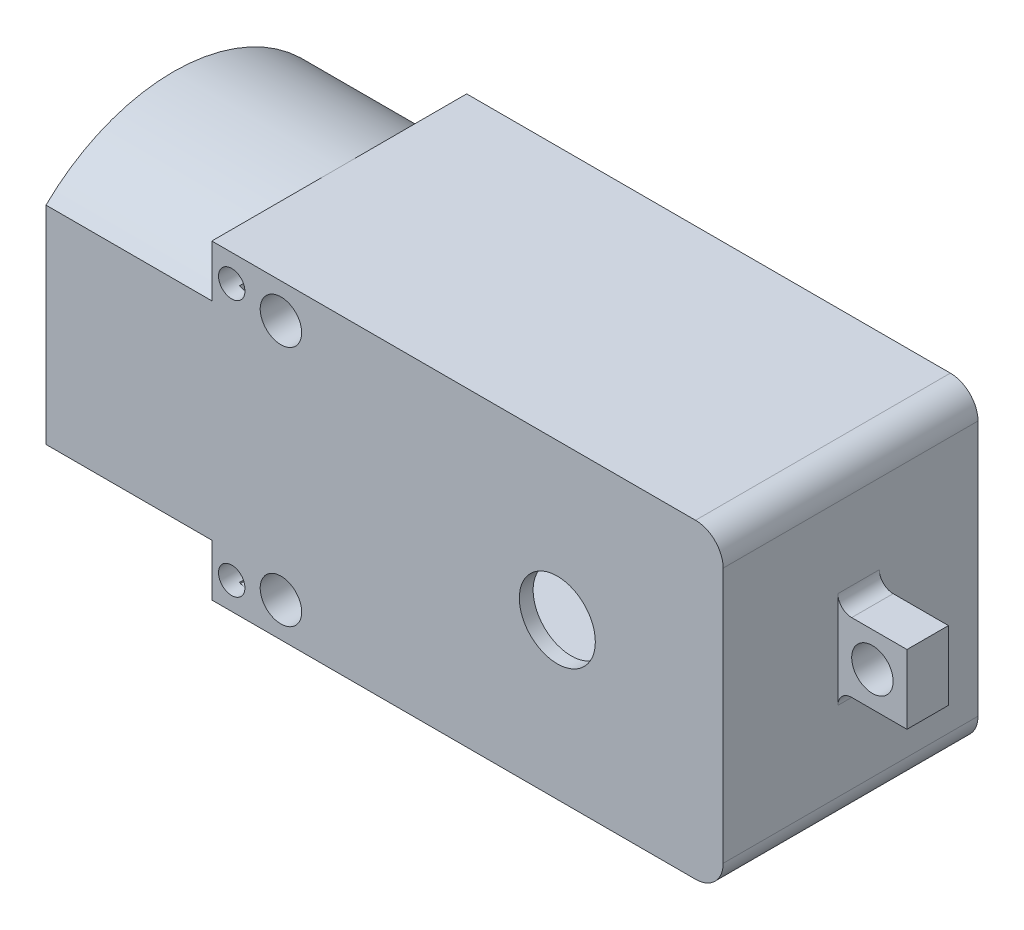
SolidWorks part; units mm, degrees
ref_plane "Front Plane" through (0, 0, 0) normal (0, 0, 1) x (1, 0, 0)
ref_plane "Top Plane" through (0, 0, 0) normal (0, 1, 0) x (1, 0, 0)
ref_plane "Right Plane" through (0, 0, 0) normal (1, 0, 0) x (0, 0, -1)
sketch "Sketch1" plane through (0, 0, 0) normal (0, 0, 1) x (1, 0, 0)
  line L1 (17.5, -11.25) -> (-17.5, -11.25)
  line L2 (19.5, -9.25) -> (19.5, 9.25)
  line L3 (17.5, 11.25) -> (-17.5, 11.25)
  line L4 (-17.5, -11.25) -> (-17.5, 11.25)
  line L5 (0, 11.25) -> (0, -11.25) construction
  line L6 (19.5, 0) -> (-17.5, 0) construction
  arc A0 (17.5, -11.25) -> (19.5, -9.25) centre (17.5, -9.25) ccw
  arc A1 (19.5, 9.25) -> (17.5, 11.25) centre (17.5, 9.25) ccw
  circle A2 centre (-12.5, 8.75) radius 1.5
  circle A3 centre (-12.5, -8.75) radius 1.5
  point P0 (0, 0)
  dimension "D1" = 2
  dimension "D4" = 3
  dimension "D6" = 17.5
  dimension "D2" = 22.5
  dimension "D3" = 37
  dimension "D5" = 5
extrude "Boss-Extrude1" add sketch "Sketch1" along normal mid plane 18.44
ref_plane "Plane1" through (0, 0, -0.58) normal (0, 0, 1) x (1, 0, 0)
sketch "Sketch2" plane through (-17.5, 0, 0) normal (-1, 0, 0) x (0, 0, 1)
  line L0 (9.22, -7.5) -> (9.22, 7.5)
  line L1 (-9.22, 11.25) -> (-9.22, -11.25) construction
  line L2 (9.22, 11.25) -> (9.22, -11.25) construction
  line L3 (0, 11.25) -> (0, -11.25) construction
  line L4 (9.22, 11.25) -> (-9.22, 11.25) construction
  line L5 (9.22, -11.25) -> (-9.22, -11.25) construction
  line L6 (-9.22, 0) -> (9.22, 0) construction
  line L7 (-9.22, -7.5) -> (-9.22, 7.5)
  arc A0 (9.22, 7.5) -> (-9.22, 7.5) centre (0, -1.9595) ccw
  arc A1 (9.22, -7.5) -> (-9.22, -7.5) centre (0, 1.9595) cw
  point P5 (9.22, 0)
  point P14 (0, 0)
  dimension "D1" = 15
extrude "Boss-Extrude2" add sketch "Sketch2" along normal blind 12
shell "Shell1" thickness 1 removed face at (-29.5, 0, 0)
sketch "Sketch3" plane through (-17.5, 0, 0) normal (-1, 0, 0) x (0, 0, 1)
  line L2 (-9.22, 7.5) -> (-9.22, -7.5)
  line L3 (9.22, -7.5) -> (9.22, 7.5)
  line L4 (-9.22, 7.5) -> (-9.22, -7.5)
  line L5 (9.22, -7.5) -> (9.22, 7.5)
  circle A0 centre (0, 0) radius 1.5
  arc A2 (9.22, 7.5) -> (-9.22, 7.5) centre (0, -1.9595) ccw
  arc A3 (-9.22, -7.5) -> (9.22, -7.5) centre (0, 1.9595) ccw
  arc A4 (9.22, 7.5) -> (-9.22, 7.5) centre (0, -1.9595) ccw
  arc A5 (-9.22, -7.5) -> (9.22, -7.5) centre (0, 1.9595) ccw
  dimension "D2" = 3
  dimension "D1" = 0
extrude "Boss-Extrude3" add sketch "Sketch3" along normal blind 1
sketch "Sketch6" plane through (0, 0, -0.58) normal (0, 0, 1) x (1, 0, 0)
  line L0 (19.5, 2.5) -> (24.5, 2.5)
  line L1 (19.5, -9.25) -> (19.5, 9.25) construction
  line L2 (24.5, 2.5) -> (24.5, -2.5)
  line L3 (24.5, -2.5) -> (19.5, -2.5)
  line L4 (24.5, 0) -> (-29.5, 0) construction
  line L5 (-29.5, 7.5) -> (-29.5, -7.5) construction
  line L6 (19.5, 2.5) -> (19.5, -2.5)
  line L7 (22, -2.5) -> (22, 2.5) construction
  circle A0 centre (22, 0) radius 1.5
  dimension "D3" = 3
  dimension "D1" = 5
  dimension "D2" = 5
extrude "Boss-Extrude4" add sketch "Sketch6" against normal blind 1.5 and the other way blind 1.5
sketch "Sketch7" plane through (0, 0, 9.22) normal (0, 0, 1) x (1, 0, 0)
  line L0 (-29.5, 0) -> (24.5, 0) construction
  line L1 (-29.5, -7.5) -> (-29.5, 7.5) construction
  line L2 (24.5, -2.5) -> (24.5, 2.5) construction
  circle A0 centre (7.5, 0) radius 2.75
  circle A1 centre (-12.5, 8.75) radius 1.5 construction
  circle A2 centre (22, 0) radius 1.5 construction
  dimension "D1" = 20
  dimension "D2" = 5.5
  dimension "D3" = 14.5
extrude "Cut-Extrude1" cut sketch "Sketch7" against normal through all
fillet "Fillet1" radius 1 2 edges at (19.5, -2.5, -0.58) (19.5, 2.5, -0.58)
sketch "Sketch8" plane through (0, 0, -0.58) normal (0, 0, 1) x (1, 0, 0)
  line L0 (17.5, 11.25) -> (-17.5, 11.25) construction
  line L1 (19.5, 0) -> (-18.5, 0) construction
  line L2 (19.5, -9.25) -> (19.5, 9.25) construction
  line L3 (-18.5, 7.0684) -> (-18.5, -7.0684) construction
  circle A0 centre (-16.062, 9.294) radius 0.956
  circle A1 centre (-16.062, -9.294) radius 0.956
  point P2 (-16.062, 10.25)
  dimension "D1" = 1
extrude "Cut-Extrude2" cut sketch "Sketch8" against normal blind 20 and the other way blind 20
